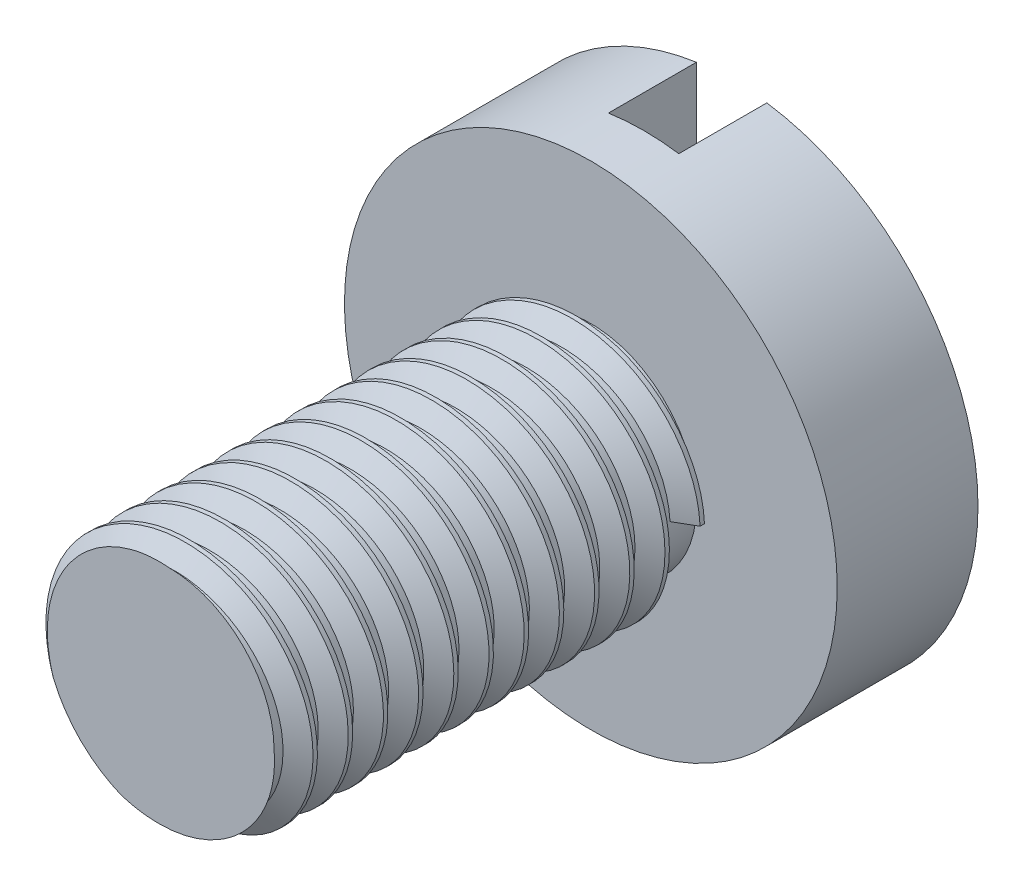
SolidWorks part; units mm, degrees
ref_plane "Front Plane" through (0, 0, 0) normal (0, 0, 1) x (1, 0, 0)
ref_plane "Top Plane" through (0, 0, 0) normal (0, 1, 0) x (1, 0, 0)
ref_plane "Right Plane" through (0, 0, 0) normal (1, 0, 0) x (0, 0, -1)
sketch "Sketch1" plane through (0, 0, 0) normal (0, 0, 1) x (1, 0, 0)
  circle A0 centre (0, 0) radius 7
  dimension "D1" = 14
extrude "Boss-Extrude1" add sketch "Sketch1" along normal blind 4
sketch "Sketch2" plane through (0, 0, 4) normal (0, 0, 1) x (1, 0, 0)
  circle A0 centre (0, 0) radius 3
  dimension "D1" = 6
extrude "Boss-Extrude2" add sketch "Sketch2" along normal blind 12
thread "Thread1" pitch 1 method extrude profile "Thread Profile1" start angle 0, offset 0, length 0, pitch 1, diameter 6
ref_plane "Plane1" through (3, 0, 4) normal (0, -1, 0) x (1, 0, 0)
sketch "Thread Profile1" plane through (3, 0, 4) normal (0, -1, 0) x (1, 0, 0)
  line L0 (0, 0) -> (0, 1) construction
  line L1 (0, 0) -> (0.5413, 0.3125)
  line L2 (0.5413, 0.3125) -> (0.5413, 0.4375)
  line L3 (0.5413, 0.4375) -> (0, 0.75)
  line L4 (0.5413, 0.375) -> (0, 0.375) construction
  line L11 (0, 0) -> (0, 0.75)
  point P2 (0, 0)
  dimension "Pitch" = 1
  dimension "Profile_Angle" = 60
  dimension "Profile_Land" = 0.125
  dimension "Profile_Height" = 0.5413
sketch "Sketch5" plane through (0, 0, 16) normal (0, 0, 1) x (1, 0, 0)
  circle A0 centre (0, 0) radius 7
  circle A1 centre (0, 0) radius 7 construction
extrude "Cut-Extrude1" cut sketch "Sketch5" along normal through all
sketch "Sketch6" plane through (0, 0, 0) normal (0, 0, -1) x (-1, 0, 0)
  line L1 (-1, -7) -> (1, -7)
  line L2 (-1, -7) -> (-1, 7)
  line L3 (-1, 7) -> (1, 7)
  line L4 (1, -7) -> (1, 7)
  line L5 (-1, -7) -> (1, 7) construction
  line L6 (-1, 7) -> (1, -7) construction
  circle A0 centre (0, 0) radius 7 construction
  point P0 (0, 0)
  dimension "D1" = 2
extrude "Cut-Extrude2" cut sketch "Sketch6" against normal blind 2.5
equation "\"pin_diameter\"=10.00"
equation "\"upper_pin_length\"=60.00"
equation "\"lower_pin_length\"=33.00"
equation "\"pin_head_diameter\"=14.00"
equation "\"pin_screw_diameter\"=6.00"
equation "\"D1@Sketch1\"=\"pin_head_diameter\""
equation "\"D1@Sketch2\"=\"pin_screw_diameter\""
